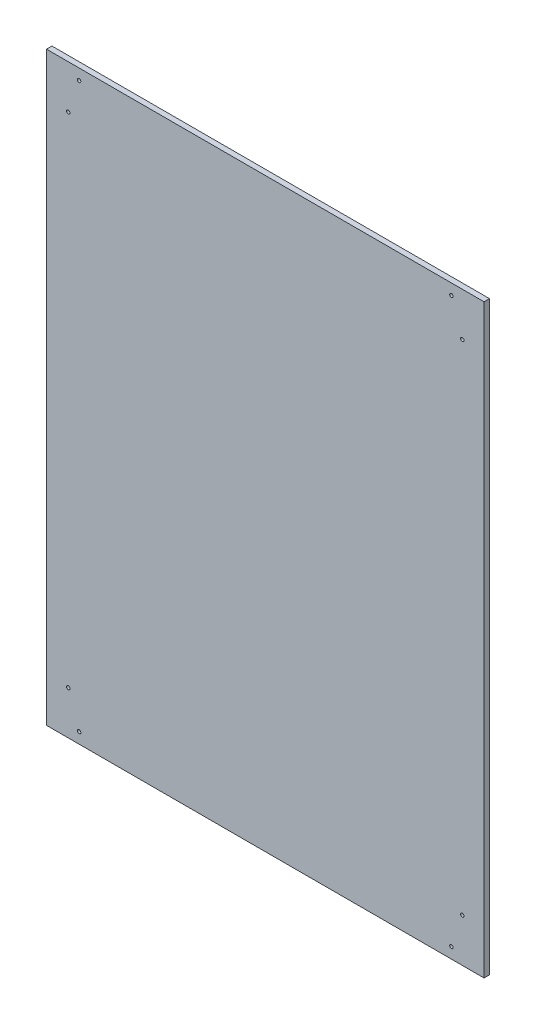
SolidWorks part; units mm, degrees
material "PE High Density Film"
ref_plane "Front Plane" through (0, 0, 0) normal (0, 0, 1) x (1, 0, 0)
ref_plane "Top Plane" through (0, 0, 0) normal (0, 1, 0) x (1, 0, 0)
ref_plane "Right Plane" through (0, 0, 0) normal (1, 0, 0) x (0, 0, -1)
sketch "Sketch1" plane through (0, 0, 0) normal (0, 0, 1) x (1, 0, 0)
  line L1 (0, 0) -> (510.54, 0)
  line L2 (0, 0) -> (0, 683.26)
  line L3 (0, 683.26) -> (510.54, 683.26)
  line L4 (510.54, 0) -> (510.54, 683.26)
  dimension "D1" = 683.26
  dimension "D2" = 510.54
extrude "Boss-Extrude1" add sketch "Sketch1" along normal blind 6.35
sketch "Sketch4" plane through (0, 0, 0) normal (0, 0, -1) x (-1, 0, 0)
  line L0 (-510.54, 683.26) -> (0, 683.26) construction
  line L1 (-510.54, 0) -> (-510.54, 683.26) construction
  line L2 (-510.54, 0) -> (0, 683.26) construction
  line L4 (-255.27, 683.26) -> (-255.27, 341.63) construction
  line L5 (-255.27, 341.63) -> (-510.54, 341.63) construction
  point P0 (-472.44, 670.56)
  point P1 (-485.14, 632.46)
  point P12 (-25.4, 632.46)
  point P14 (-38.1, 670.56)
  point P15 (-25.4, 50.8)
  point P16 (-38.1, 12.7)
  point P17 (-485.14, 50.8)
  point P18 (-472.44, 12.7)
  dimension "D1" = 12.7
  dimension "D2" = 38.1
  dimension "D3" = 25.4
  dimension "D4" = 50.8
hole_wizard "#10-32 Tapped Hole2" positions "Sketch4" profile "Sketch5" tap size "#10-32" standard "ANSI Inch" end condition through all
sketch "Sketch5" plane through (472.44, 670.56, 0) normal (1, 0, 0) x (0, 1, 0)
  line L0 (0, 0) -> (0, 6.35)
  line L1 (0, 6.35) -> (2.0193, 6.35)
  line L2 (2.0193, 6.35) -> (2.0193, 0)
  line L5 (2.0193, 0) -> (0, 0)
  line L11 (0, -6.35) -> (0, 107.95) construction
  dimension "Thru Tap Drill Dia." = 4.0386
  dimension "Thru Tap Drill Depth" = 6.35
cosmetic thread "Hole Thread3" parameters "D2"=4.826
cosmetic thread "Hole Thread4" parameters "D2"=4.826
cosmetic thread "Hole Thread5" parameters "D2"=4.826
cosmetic thread "Hole Thread6" parameters "D2"=4.826
cosmetic thread "Hole Thread7" parameters "D2"=4.826
cosmetic thread "Hole Thread8" parameters "D2"=4.826
cosmetic thread "Hole Thread9" parameters "D2"=4.826
cosmetic thread "Hole Thread10" parameters "D2"=4.826
